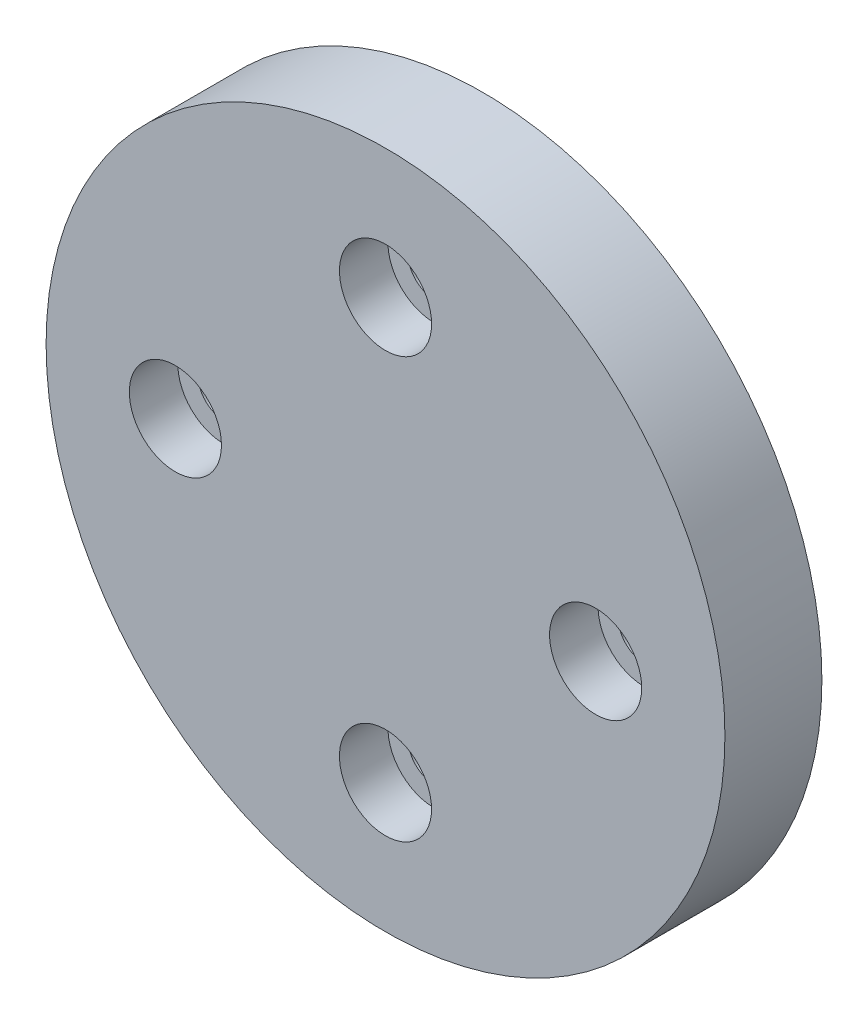
SolidWorks part; units mm, degrees
ref_plane "Front Plane" through (0, 0, 0) normal (1, 0, 0) x (0, 1, 0)
ref_plane "Top Plane" through (0, 0, 0) normal (0, 0, 1) x (0, 1, 0)
ref_plane "Right Plane" through (0, 0, 0) normal (0, 1, 0) x (-1, 0, 0)
sketch "Sketch1" plane through (0, 0, 0) normal (0, 0, 1) x (0, 1, 0)
  circle A0 centre (0, 0) radius 21
  circle A1 centre (0, 0) radius 13 construction
  circle A2 centre (0, 13) radius 1.6
  circle A3 centre (0, 13) radius 2.85
  circle A4 centre (13, 0) radius 2.85
  circle A5 centre (13, 0) radius 1.6
  circle A6 centre (0, -13) radius 2.85
  circle A7 centre (0, -13) radius 1.6
  circle A8 centre (-13, 0) radius 2.85
  circle A9 centre (-13, 0) radius 1.6
  point P19 (0, 0)
  dimension "D1" = 42
  dimension "D2" = 26
  dimension "D3" = 3.2
  dimension "D4" = 5.7
  dimension "D5" = 4
extrude "Boss-Extrude1" add sketch "Sketch1" along normal blind 6 contours A0 A8 A6 A4 A3 region at (0, 0, 0)
extrude "Boss-Extrude2" add sketch "Sketch1<4>" along normal blind 3 contours A8 A9 | A3 A2 | A4 A5 | A6 A7 region at (-13, -2.7694, 0) region at (0, 10.2306, 0) region at (13, -2.7694, 0) region at (0, -15.7694, 0)
sketch "Sketch1<4>" plane through (0, 0, 0) normal (0, 0, 1) x (0, 1, 0) same geometry as "Sketch1"
